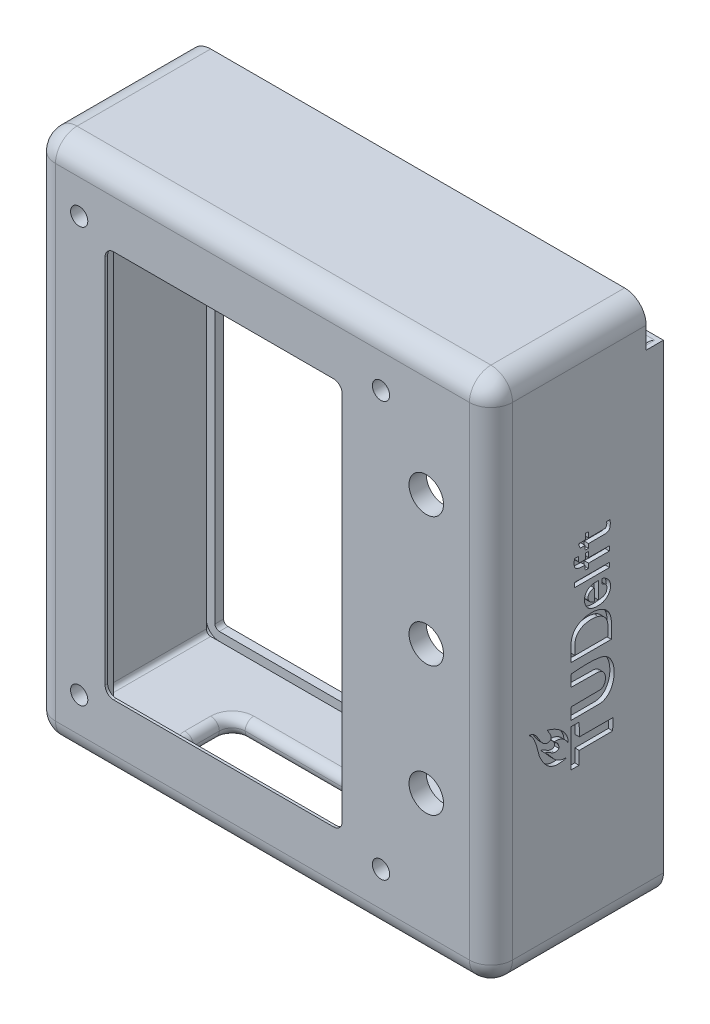
SolidWorks part; units mm, degrees
ref_plane "Front Plane" through (0, 0, 0) normal (0, 0, 1) x (1, 0, 0)
ref_plane "Top Plane" through (0, 0, 0) normal (0, 1, 0) x (1, 0, 0)
ref_plane "Right Plane" through (0, 0, 0) normal (1, 0, 0) x (0, 0, -1)
sketch "Sketch2" plane through (0, 0, 0) normal (0, 0, 1) x (1, 0, 0)
  line L1 (5, 0) -> (101, 0)
  line L2 (0, 5) -> (0, 117)
  line L3 (5, 122) -> (101, 122)
  line L4 (106, 5) -> (106, 117)
  arc A6 (5, 0) -> (0, 5) centre (5, 5) cw
  arc A7 (101, 0) -> (106, 5) centre (101, 5) ccw
  arc A8 (0, 117) -> (5, 122) centre (5, 117) cw
  arc A9 (101, 122) -> (106, 117) centre (101, 117) cw
  point P20 (0, 0)
  point P23 (106, 0)
  point P26 (0, 122)
  dimension "D11" = 5
  dimension "D1" = 122
  dimension "D2" = 106
extrude "Boss-Extrude1" add sketch "Sketch2" against normal blind 40
shell "Shell1" thickness 4 removed face at (53, 61, -40)
sketch "Sketch4" plane through (0, 0, -4) normal (0, 0, -1) x (-1, 0, 0)
  line L4 (-5, 4) -> (-101, 4) construction
  line L7 (-45.75, 118) -> (-45.75, 4) construction
  line L14 (-102, 61) -> (-4, 61) construction
  line L15 (-102, 5) -> (-102, 117) construction
  line L16 (-4, 117) -> (-4, 5) construction
  line L18 (-101, 118) -> (-5, 118) construction
  line L19 (-5, 4) -> (-101, 4) construction
  line L21 (-4, 117) -> (-4, 5) construction
  line L26 (-73.5, 9) -> (-73.5, 108)
  line L27 (-73.5, 108) -> (-14.5, 108)
  line L28 (-14.5, 9) -> (-14.5, 108)
  line L29 (-73.5, 9) -> (-14.5, 9)
  circle A7 centre (-91, 93.5) radius 4
  circle A8 centre (-91, 63.5) radius 4
  circle A9 centre (-91, 33.5) radius 4
  circle A28 centre (-10.5, 13) radius 2
  circle A29 centre (-80.5, 13) radius 2
  circle A30 centre (-80.5, 109.15) radius 2
  circle A31 centre (-10.5, 109.15) radius 2
  dimension "D5" = 8
  dimension "D15" = 1.15
  dimension "D12" = 4
  dimension "D13" = 7
  dimension "D2" = 17.5
  dimension "D3" = 99
  dimension "D4" = 59
  dimension "D6" = 5
  dimension "D8" = 30
  dimension "D9" = 10.5
  dimension "D10" = 24.5
  dimension "D11" = 41.75
  dimension "D16" = 4
  dimension "4" = 4
  dimension "D7" = 3
extrude "Cut-Extrude2" cut sketch "Sketch4" against normal blind 10
fillet "Fillet10" radius 5 8 edges at (106, 61, 0) (104.5355, 1.4645, 0) (53, 0, 0) (104.5355, 120.5355, 0) (1.4645, 1.4645, 0) (0, 61, 0) (1.4645, 120.5355, 0) (53, 122, 0)
sketch "Sketch13" plane through (102, 0, 0) normal (-1, 0, 0) x (0, 0, 1)
  line L0 (-14, 118) -> (-4, 118)
  line L1 (-14, 118) -> (-14, 4)
  line L2 (-14, 4) -> (-4, 4)
  line L3 (-4, 118) -> (-4, 4)
  line L4 (-40, 118) -> (-4, 118) construction
  line L5 (-4, 5) -> (-4, 117) construction
  line L6 (-40, 4) -> (-4, 4) construction
  dimension "D1" = 10
  dimension "D2" = 0
  dimension "D3" = 0
  dimension "D4" = 0
extrude "Boss-Extrude5" add sketch "Sketch13" along normal blind 4.5
sketch "Sketch14" plane through (0, 0, -14) normal (0, 0, -1) x (-1, 0, 0)
  line L0 (-97.5, 118) -> (-97.5, 4) construction
  circle A0 centre (-99.5, 87.5) radius 1.65
  circle A1 centre (-99.5, 101.5) radius 1.65
  circle A2 centre (-91, 93.5) radius 4 construction
  circle A3 centre (-99.5, 71.5) radius 1.65
  circle A4 centre (-99.5, 57.5) radius 1.65
  circle A5 centre (-99.5, 41.5) radius 1.65
  circle A6 centre (-99.5, 27.5) radius 1.65
  circle A7 centre (-91, 63.5) radius 4 construction
  dimension "D1" = 3.3
  dimension "D2" = 3.3
  dimension "D3" = 8
  dimension "D4" = 6
  dimension "D5" = 2
  dimension "D6" = 2
  dimension "D8" = 6
  dimension "D7" = 3
extrude "Cut-Extrude7" cut sketch "Sketch14" against normal blind 6
sketch "Sketch17" plane through (0, 122, 0) normal (0, 1, 0) x (1, 0, 0)
  line L0 (101, 40) -> (5, 40) construction
  line L1 (2, 38) -> (104, 38)
  line L2 (2, 38) -> (2, 36)
  line L3 (2, 36) -> (104, 36)
  line L4 (104, 38) -> (104, 36)
  line L5 (106, 40) -> (106, 5) construction
  line L6 (0, 40) -> (0, 5) construction
  dimension "D1" = 2
  dimension "D2" = 2
  dimension "D3" = 2
  dimension "D4" = 2
extrude "Cut-Extrude10" cut sketch "Sketch17" against normal blind 120
fillet "Fillet14" radius 3 2 edges at (2, 2, -37) (104, 2, -37)
sketch "Sketch18" plane through (0, 122, 0) normal (0, 1, 0) x (1, 0, 0)
  line L1 (4, 40) -> (102, 40)
  line L2 (4, 40) -> (4, 38)
  line L3 (4, 38) -> (102, 38)
  line L4 (102, 40) -> (102, 38)
  line L5 (101, 40) -> (101, 38) construction
  dimension "D1" = 1
extrude "Cut-Extrude11" cut sketch "Sketch18" against normal blind 8.5
sketch "Sketch29" plane through (0, 0, 0) normal (-1, 0, 0) x (0, 0, 1)
  line L0 (-27, 117) -> (-27, 5) construction
  line L1 (-40, 117) -> (-5, 117) construction
  line L2 (-40, 5) -> (-5, 5) construction
  line L3 (-40, 117) -> (-40, 5) construction
  text T0 "<b>EduPace</b>" font "Helvetica" height in points 36
  dimension "D1" = 13
extrude "Cut-Extrude15" cut sketch "Sketch29" against normal blind 1
sketch "Sketch21" plane through (106, 0, 0) normal (1, 0, 0) x (0, 0, -1)
  line L0 (18.5658, 36.3938) -> (18.5965, 45.0875)
  line L1 (18.5965, 45.0875) -> (20.4704, 45.0568)
  line L2 (20.4704, 45.0568) -> (20.5012, 42.077)
  line L3 (20.5012, 42.077) -> (28.2733, 42.0462)
  line L4 (28.2733, 42.0462) -> (28.2426, 39.4043)
  line L5 (28.2426, 39.4043) -> (20.4704, 39.3736)
  line L6 (20.4704, 39.3736) -> (20.4397, 36.3938)
  line L7 (20.4397, 36.3938) -> (18.5658, 36.3938)
  line L8 (8.889, 48.0059) -> (8.9504, 48.1595)
  line L9 (13.1284, 47.0229) -> (13.1898, 47.0843)
  line L10 (14.6951, 44.0123) -> (14.6951, 43.9202)
  line L11 (17.3677, 39.4043) -> (17.3677, 39.2814)
  line L12 (18.5658, 46.347) -> (18.6272, 49.0504)
  line L13 (18.5658, 52.9826) -> (18.6272, 55.6552)
  line L14 (27.9217, 57.9553) -> (18.5462, 57.9553)
  line L15 (27.1117, 58.9378) -> (19.482, 58.9378)
  line L16 (24.9204, 71.2566) -> (24.9716, 67.3142)
  line L17 (25.7652, 70.1558) -> (25.7908, 71.2566)
  line L18 (24.0525, 70.1828) -> (24.0282, 67.5039)
  line L19 (19.4164, 72.5878) -> (19.4164, 73.6374)
  line L20 (19.4164, 73.6374) -> (27.5316, 73.6374)
  line L21 (27.5316, 73.6374) -> (27.506, 72.5878)
  line L22 (27.506, 72.5878) -> (19.4164, 72.5878)
  line L23 (19.3652, 78.4502) -> (20.2612, 78.4246)
  line L24 (21.874, 76.991) -> (21.8996, 78.2966)
  line L25 (21.8996, 78.2966) -> (22.642, 78.271)
  line L26 (22.642, 78.271) -> (22.6676, 76.991)
  line L27 (22.6676, 76.991) -> (27.5316, 76.9654)
  line L28 (27.5316, 76.9654) -> (27.4804, 75.9158)
  line L29 (27.4804, 75.9158) -> (22.642, 75.8902)
  line L30 (22.642, 75.8902) -> (22.6164, 74.8406)
  line L31 (22.6164, 74.8406) -> (21.874, 74.8662)
  line L32 (21.874, 74.8662) -> (21.8484, 75.9158)
  line L33 (20.3636, 80.831) -> (20.3892, 80.9334)
  line L34 (20.3892, 80.9334) -> (21.874, 80.959)
  line L35 (21.874, 80.959) -> (21.8996, 82.239)
  line L36 (21.8996, 82.239) -> (22.642, 82.2134)
  line L37 (22.642, 82.2134) -> (22.6676, 80.9334)
  line L38 (26.7892, 82.0598) -> (26.8148, 82.1878)
  line L39 (26.8148, 82.1878) -> (27.634, 82.1622)
  line L40 (22.642, 79.8326) -> (22.6164, 78.8854)
  line L41 (22.6164, 78.8854) -> (21.874, 78.911)
  line L42 (21.874, 78.911) -> (21.8484, 79.8582)
  line L43 (21.8484, 79.8582) -> (20.6708, 79.8838)
  line L44 (20.6708, 79.8838) -> (20.3636, 80.831)
  arc A0 (14.6951, 44.0123) -> (17.9207, 42.0462) centre (14.9851, 40.8591) cw
  spline S0 degree 3 poles (8.9504, 48.1595) (10.8447, 48.0332) (11.0445, 45.4044) (12.6368, 44.6267) (12.8229, 44.5358) (13.0468, 44.5014) (13.2512, 44.5346) (14.7979, 44.7854) (13.3973, 46.485) (13.1284, 47.0229) knots 0 0 0 0 1 1 1 2 2 2 3 3 3 3
  spline S1 degree 3 poles (13.1898, 47.0843) (15.4649, 46.4945) (18.0438, 44.6324) (17.9207, 42.0462) knots 0 0 0 0 1 1 1 1
  spline S2 degree 3 poles (14.6951, 43.9202) (15.4912, 43.3412) (15.7273, 43.1257) (15.7703, 42.1384) knots 0 0 0 0 1 1 1 1
  spline S3 degree 3 poles (15.7703, 42.1384) (14.6875, 41.154) (13.6621, 42.6032) (12.514, 42.845) knots 0 0 0 0 1 1 1 1
  spline S4 degree 3 poles (12.514, 42.845) (14.5613, 41.0987) (14.538, 39.6064) (17.3677, 39.4043) knots 0 0 0 0 1 1 1 1
  spline S5 degree 3 poles (17.3677, 39.2814) (15.5498, 38.9333) (14.1202, 38.8539) (12.7597, 40.3259) (12.0493, 41.0946) (11.5119, 42.0427) (11.1623, 43.0293) (11.0568, 43.3267) (10.2237, 47.6722) (8.889, 48.0059) knots 0 0 0 0 1 1 1 2 2 2 3 3 3 3
  spline S6 degree 3 poles (18.6272, 49.0504) (20.7981, 49.0709) (22.9691, 49.0814) (25.1399, 49.1118) (26.9659, 49.1374) (26.9859, 52.1637) (25.4778, 52.7368) (25.1849, 52.8481) (24.8693, 52.91) (24.5562, 52.9211) (22.5605, 52.9921) (20.5626, 52.9621) (18.5658, 52.9826) knots 0 0 0 0 1 1 1 2 2 2 3 3 3 4 4 4 4
  spline S7 degree 3 poles (18.6272, 55.6552) (18.8649, 55.6531) (24.4355, 56.3234) (26.5223, 55.2251) (29.2439, 53.7927) (29.2543, 48.3438) (26.6144, 46.8078) (25.8015, 46.3348) (25.2427, 46.3595) (24.2797, 46.347) (22.3752, 46.3224) (20.4704, 46.347) (18.5658, 46.347) knots 0 0 0 0 1 1 1 2 2 2 3 3 3 4 4 4 4
  spline S8 degree 3 poles (18.5462, 57.9553) (18.5561, 59.2706) (18.5563, 60.5861) (18.5759, 61.9013) (18.5761, 61.9153) (18.6034, 61.9171) (18.6056, 61.931) (18.6237, 62.0487) (18.6171, 62.1693) (18.6352, 62.287) (18.6374, 62.3008) (18.6618, 62.303) (18.6649, 62.3167) (18.692, 62.4339) (18.6972, 62.5555) (18.7242, 62.6727) (18.7274, 62.6863) (18.7495, 62.6891) (18.7539, 62.7024) (18.7995, 62.839) (18.8271, 62.9811) (18.8726, 63.1177) (18.877, 63.131) (18.896, 63.1349) (18.9023, 63.1474) (18.9952, 63.3334) (19.0763, 63.5251) (19.1693, 63.7111) (19.1755, 63.7236) (19.1909, 63.7293) (19.199, 63.7408) (19.2603, 63.8284) (19.3156, 63.9202) (19.377, 64.0078) (19.6359, 64.3777) (20.038, 64.662) (20.4154, 64.8979) (20.5667, 64.9924) (20.7475, 65.1038) (20.9198, 65.1649) (21.3978, 65.3345) (21.8926, 65.5068) (22.4032, 65.5506) (22.9354, 65.5962) (23.4728, 65.6212) (24.0054, 65.5803) (24.0193, 65.5792) (24.0212, 65.5526) (24.035, 65.5506) (24.1627, 65.5324) (24.2931, 65.5392) (24.4207, 65.5209) (24.4346, 65.519) (24.4367, 65.4942) (24.4504, 65.4913) (24.5776, 65.464) (24.7089, 65.4592) (24.8361, 65.4319) (24.8498, 65.429) (24.8525, 65.4067) (24.8658, 65.4023) (25.0617, 65.337) (25.2632, 65.2895) (25.4591, 65.2242) (25.4724, 65.2198) (25.4763, 65.2008) (25.4888, 65.1946) (25.8705, 65.0037) (26.2466, 64.8663) (26.5569, 64.5715) (26.8843, 64.2605) (27.168, 63.9847) (27.3876, 63.5924) (27.8171, 62.8256) (27.9449, 61.9067) (27.9514, 61.0409) (27.959, 60.0123) (27.9316, 58.9838) (27.9217, 57.9553) knots 0 0 0 0 1 1 1 2 2 2 3 3 3 4 4 4 5 5 5 6 6 6 7 7 7 8 8 8 9 9 9 10 10 10 11 11 11 12 12 12 13 13 13 14 14 14 15 15 15 16 16 16 17 17 17 18 18 18 19 19 19 20 20 20 21 21 21 22 22 22 23 23 23 24 24 24 25 25 25 26 26 26 26
  spline S9 degree 3 poles (19.482, 58.9378) (19.4958, 60.1067) (19.2393, 61.6215) (19.8988, 62.7206) (20.3977, 63.5522) (21.3341, 64.0441) (22.271, 64.1953) (22.4621, 64.2261) (22.656, 64.2354) (22.8481, 64.2594) (22.9126, 64.2674) (22.9754, 64.2914) (23.0404, 64.2914) (23.721, 64.2914) (24.2987, 64.257) (24.9318, 64.067) (24.9463, 64.0627) (24.9497, 64.0401) (24.9639, 64.035) (25.0687, 63.9968) (25.1796, 63.9769) (25.2845, 63.9388) (25.2987, 63.9336) (25.303, 63.9135) (25.3165, 63.9067) (25.6193, 63.7553) (25.8972, 63.6286) (26.15, 63.3938) (26.3026, 63.2522) (26.523, 63.0466) (26.6309, 62.8488) (26.8177, 62.5063) (27.0336, 62.0977) (27.0797, 61.6948) (27.1125, 61.4073) (27.1404, 61.1185) (27.1438, 60.8292) (27.1511, 60.1987) (27.1224, 59.5683) (27.1117, 58.9378) knots 0 0 0 0 1 1 1 2 2 2 3 3 3 4 4 4 5 5 5 6 6 6 7 7 7 8 8 8 9 9 9 10 10 10 11 11 11 12 12 12 13 13 13 13
  spline S10 degree 3 poles (25.7908, 71.2566) (28.7835, 70.3214) (28.1943, 66.3595) (25.0228, 66.239) (24.394, 66.2152) (23.6102, 66.2654) (23.026, 66.5718) (21.5382, 67.3523) (21.1576, 69.7508) (22.5908, 70.7958) (23.2954, 71.3096) (24.0969, 71.3176) (24.9204, 71.2566) knots 0 0 0 0 1 1 1 2 2 2 3 3 3 4 4 4 4
  spline S11 degree 3 poles (24.9716, 67.3142) (25.675, 67.4373) (26.6363, 67.4622) (26.8404, 68.3638) (27.0632, 69.3477) (26.6379, 69.8286) (25.7652, 70.1558) knots 0 0 0 0 1 1 1 2 2 2 2
  spline S12 degree 3 poles (24.0282, 67.5039) (21.8404, 67.7774) (22.2114, 70.551) (24.0525, 70.1828) knots 0 0 0 0 1 1 1 1
  spline S13 degree 3 poles (21.8484, 75.9158) (19.8454, 75.9529) (19.0012, 76.084) (19.3652, 78.4502) knots 0 0 0 0 1 1 1 1
  spline S14 degree 3 poles (20.2612, 78.4246) (20.2612, 77.8978) (20.0868, 77.0498) (20.85, 77.0166) (21.1911, 77.0018) (21.5327, 76.9996) (21.874, 76.991) knots 0 0 0 0 1 1 1 2 2 2 2
  spline S15 degree 3 poles (22.6676, 80.9334) (23.9305, 80.942) (25.1936, 80.9421) (26.4564, 80.959) (26.8463, 80.9643) (26.9557, 81.8934) (26.7892, 82.0598) knots 0 0 0 0 1 1 1 2 2 2 2
  spline S16 degree 3 poles (27.634, 82.1622) (27.7144, 81.1569) (27.8395, 79.8825) (26.482, 79.8582) (25.2022, 79.8354) (23.922, 79.8412) (22.642, 79.8326) knots 0 0 0 0 1 1 1 2 2 2 2
extrude "Cut-Extrude13" cut sketch "Sketch21" against normal blind 1
sketch "Sketch22" plane through (0, 4, 0) normal (0, 1, 0) x (1, 0, 0)
  line L0 (5, 4) -> (97.5, 4) construction
  line L1 (26, 23) -> (65, 23)
  line L2 (23, 20) -> (23, 14)
  line L3 (26, 11) -> (65, 11)
  line L4 (68, 20) -> (68, 14)
  line L5 (5, 36) -> (5, 4) construction
  arc A0 (65, 11) -> (68, 14) centre (65, 14) ccw
  arc A1 (65, 23) -> (68, 20) centre (65, 20) cw
  arc A2 (23, 14) -> (26, 11) centre (26, 14) ccw
  arc A3 (26, 23) -> (23, 20) centre (26, 20) ccw
  point P12 (68, 23)
  point P15 (23, 11)
  point P18 (23, 23)
  dimension "D5" = 3
  dimension "D1" = 12
  dimension "D2" = 45
  dimension "D3" = 7
  dimension "D4" = 18
extrude "Cut-Extrude14" cut sketch "Sketch22" against normal blind 10
sketch "Sketch28" plane through (0, 0, 0) normal (0, 0, 1) x (1, 0, 0)
  line L1 (14.5, 108) -> (73.5, 108)
  line L2 (14.5, 108) -> (14.5, 9)
  line L3 (14.5, 9) -> (73.5, 9)
  line L4 (73.5, 108) -> (73.5, 9)
  line L5 (18.5, 106) -> (69.5, 106)
  line L6 (16.5, 104) -> (16.5, 18)
  line L7 (18.5, 16) -> (69.5, 16)
  line L8 (71.5, 104) -> (71.5, 18)
  arc A0 (16.5, 18) -> (18.5, 16) centre (18.5, 18) ccw
  arc A1 (69.5, 16) -> (71.5, 18) centre (69.5, 18) ccw
  arc A2 (69.5, 106) -> (71.5, 104) centre (69.5, 104) cw
  arc A3 (18.5, 106) -> (16.5, 104) centre (18.5, 104) ccw
  dimension "D5" = 2
  dimension "D1" = 2
  dimension "D2" = 2
  dimension "D3" = 2
  dimension "D4" = 7
extrude "Boss-Extrude7" add sketch "Sketch28" against normal blind 0.6
sketch "Sketch33" plane through (0, 122, 0) normal (0, 1, 0) x (1, 0, 0)
  line L0 (0, 40) -> (0, 5) construction
  line L1 (0, 38) -> (106, 38)
  line L2 (0, 38) -> (0, 36)
  line L3 (0, 36) -> (106, 36)
  line L4 (106, 38) -> (106, 36)
  line L5 (106, 40) -> (106, 5) construction
  line L6 (5, 40) -> (101, 40) construction
  dimension "D1" = 2
  dimension "D2" = 2
extrude "Cut-Extrude18" cut sketch "Sketch33" against normal blind 10
sketch "Sketch34" plane through (0, 122, 0) normal (0, 1, 0) x (1, 0, 0)
  line L1 (0, 40) -> (106, 40)
  line L2 (0, 40) -> (0, 38)
  line L3 (0, 38) -> (106, 38)
  line L4 (106, 40) -> (106, 38)
extrude "Cut-Extrude19" cut sketch "Sketch34" against normal blind 10
fillet "Fillet16" radius 1 4 edges at (3, 112, -38) (2, 112, -37) (103, 112, -38) (104, 112, -37)
fillet "Fillet17" radius 2 16 edges at (67.1213, 4, -22.1213) (68, 4, -17) (67.1213, 4, -11.8787) (45.5, 4, -11) (23.8787, 4, -11.8787) (23, 4, -17) (23.8787, 4, -22.1213) (23.8787, 0, -22.1213) (23, 0, -17) (23.8787, 0, -11.8787) (45.5, 0, -11) (67.1213, 0, -11.8787) (68, 0, -17) (67.1213, 0, -22.1213) (45.5, 4, -23) (45.5, 0, -23)
